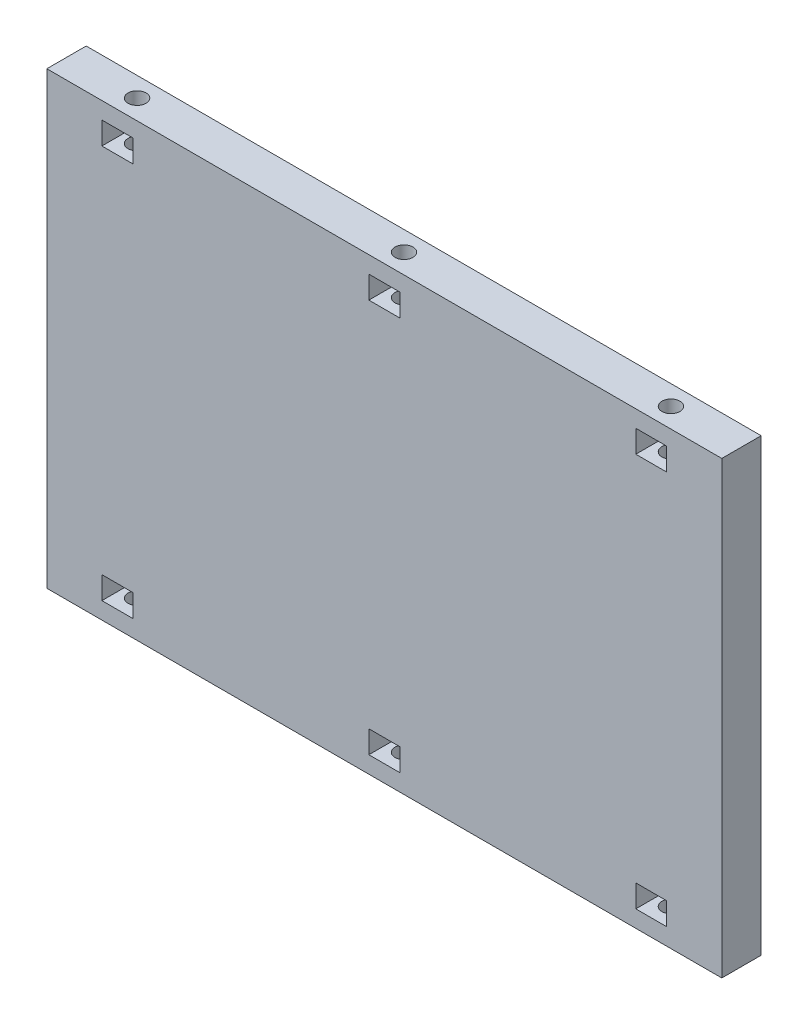
SolidWorks part; units mm, degrees
ref_plane "Plano frontal" through (0, 0, 0) normal (0, 0, 1) x (1, 0, 0)
ref_plane "Plano superior" through (0, 0, 0) normal (0, 1, 0) x (1, 0, 0)
ref_plane "Plano direito" through (0, 0, 0) normal (1, 0, 0) x (0, 0, -1)
sketch "Esboço1" plane through (0, 0, 0) normal (0, 0, 1) x (1, 0, 0)
  line L0 (-50.21, -37) -> (-60, -37) construction
  line L5 (-60, 40) -> (60, 40)
  line L6 (-60, 40) -> (-60, -40)
  line L8 (-60, -40) -> (60, -40)
  line L10 (-18.85, 0) -> (-29.82, 0) construction
  line L11 (60, 40) -> (60, -40)
  line L31 (0.18, 0) -> (34.63, 0) construction
  line L36 (34.63, 0) -> (34.63, 10.1) construction
  line L37 (34.63, 10.1) -> (30.33, 10.1) construction
  line L38 (34.63, 0) -> (34.63, -4.9) construction
  line L43 (-60, 40) -> (60, -40) construction
  line L44 (-60, -40) -> (60, 40) construction
  line L45 (-14.17, 4.9) -> (-18.67, 4.9) construction
  line L76 (34.63, 4.9) -> (39.21, 4.9) construction
  line L112 (-7.0787, 10.1) -> (-7.0787, 13.1) construction
  line L113 (-2.2667, -10.1) -> (-2.2667, -13.1) construction
  line L125 (-50.21, -40) -> (-50.21, -37) construction
  line L126 (0, 0) -> (0, -40) construction
  line L127 (-50.21, -37) -> (-44.71, -37)
  line L128 (-50.21, -37) -> (-50.21, -33)
  line L129 (-50.21, -33) -> (-44.71, -33)
  line L130 (-44.71, -37) -> (-44.71, -33)
  line L132 (50.21, -37) -> (50.21, -33)
  line L133 (50.21, -33) -> (44.71, -33)
  line L134 (44.71, -37) -> (44.71, -33)
  line L135 (50.21, -37) -> (44.71, -37)
  line L136 (-50.21, -37) -> (-44.71, -33) construction
  line L138 (-47.46, -35) -> (50.21, -35) construction
  line L139 (34.63, 0) -> (60, 0) construction
  line L140 (-2.75, -33) -> (2.75, -33)
  line L141 (-2.75, -33) -> (-2.75, -37)
  line L142 (-2.75, -37) -> (2.75, -37)
  line L143 (2.75, -33) -> (2.75, -37)
  line L144 (-2.75, -33) -> (2.75, -37) construction
  line L145 (-2.75, -37) -> (2.75, -33) construction
  line L146 (50.21, 37) -> (44.71, 37)
  line L147 (44.71, 37) -> (44.71, 33)
  line L148 (50.21, 33) -> (44.71, 33)
  line L149 (50.21, 37) -> (50.21, 33)
  line L150 (-2.75, 37) -> (2.75, 37)
  line L151 (2.75, 33) -> (2.75, 37)
  line L152 (-2.75, 33) -> (2.75, 33)
  line L153 (-2.75, 33) -> (-2.75, 37)
  line L154 (-50.21, 37) -> (-50.21, 33)
  line L155 (-50.21, 33) -> (-44.71, 33)
  line L156 (-44.71, 37) -> (-44.71, 33)
  line L157 (-50.21, 37) -> (-44.71, 37)
  point P0 (0, 0)
  point P1 (0, 0)
  point P22 (0, -35)
  point P35 (0, 0)
  dimension "D3" = 120
  dimension "D4" = 80
  dimension "D5" = 5.5
  dimension "D6" = 34.45
  dimension "D7" = 4.3
  dimension "D8" = 10.1
  dimension "D11" = 4.9
  dimension "D13" = 3
  dimension "D14" = 4.5
  dimension "D15" = 10.97
  dimension "D16" = 4
  dimension "D17" = 5.5
  dimension "D18" = 4
  dimension "D19" = 3
  dimension "D20" = 4.58
  dimension "D21" = 3
extrude "Ressalto-extrusão4" add sketch "Esboço1" along normal blind 7 contours L143 L140 L141 L142 | L135 L132 L133 L134 | L157 L154 L155 L156 | L153 L152 L151 L150 | L149 L146 L147 L148 | L6 L5 L11 L8 | L127 L130 L129 L128 region at (47.46, -35, 0) region at (0, -35, 0) region at (47.46, 35, 0) region at (0, 35, 0) region at (-47.46, 35, 0)
sketch "Esboço2" plane through (0, 40, 0) normal (0, 1, 0) x (1, 0, 0)
  line L0 (0, 0) -> (0, -7) construction
  line L1 (-60, -7) -> (60, -7) construction
  line L2 (-60, -3.5) -> (-47.46, -3.5) construction
  line L3 (-60, -7) -> (-60, 0) construction
  circle A0 centre (-47.46, -3.5) radius 1.6
  circle A1 centre (0, -3.5) radius 1.6
  circle A2 centre (47.46, -3.5) radius 1.6
  dimension "D2" = 3.2
  dimension "D3" = 3.2
  dimension "D1" = 12.54
extrude "Corte-extrusão1" cut sketch "Esboço2" along normal blind 10 from surface starting at face at (0, -40, 3.5)
extrude "Corte-extrusão2" cut sketch "Esboço2<2>" against normal blind 10
sketch "Esboço2<2>" plane through (0, 40, 0) normal (0, 1, 0) x (1, 0, 0) same geometry as "Esboço2"
